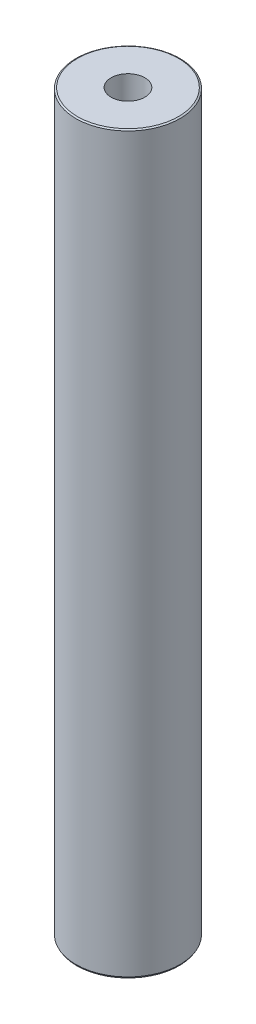
SolidWorks part; units mm, degrees
ref_plane "Front Plane" through (0, 0, 0) normal (0, 0, 1) x (1, 0, 0)
ref_plane "Top Plane" through (0, 0, 0) normal (0, 1, 0) x (1, 0, 0)
ref_plane "Right Plane" through (0, 0, 0) normal (1, 0, 0) x (0, 0, -1)
sketch "Sketch1" plane through (0, 0, 0) normal (0, 1, 0) x (1, 0, 0)
  circle A0 centre (0, 0) radius 42.5
  dimension "SHAFT_OD" = 85
extrude "Boss-Extrude1" add sketch "Sketch1" along normal blind 600
sketch "Sketch2" plane through (0, 0, 0) normal (0, 1, 0) x (1, 0, 0)
  circle A0 centre (0, 0) radius 13.7813
  dimension "BORE_D" = 27.5627
extrude "Cut-Extrude1" cut sketch "Sketch2" along normal through all
chamfer "Chamfer1" distance 0.7407 angle 60 2 edges at (0, 600, 42.5) (0, 0, 42.5) first distance on face at (0, 600, 42.5) first distance on face at (0, 0, 13.7813)
